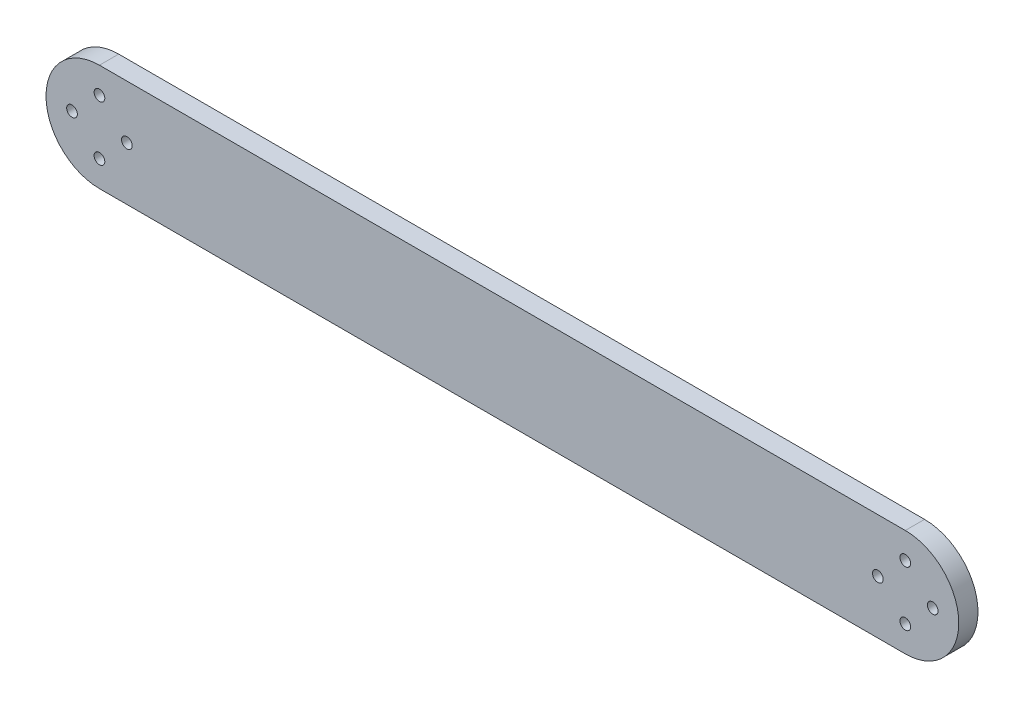
SolidWorks part; units mm, degrees
ref_plane "Front Plane" through (0, 0, 0) normal (0, 0, 1) x (1, 0, 0)
ref_plane "Top Plane" through (0, 0, 0) normal (0, 1, 0) x (1, 0, 0)
ref_plane "Right Plane" through (0, 0, 0) normal (1, 0, 0) x (0, 0, -1)
sketch "Sketch1" plane through (0, 0, 0) normal (0, 0, 1) x (1, 0, 0)
  line L1 (-55.8976, 0) -> (-50.0514, 0) construction
  line L2 (-15, 0.3576) -> (-15, 39.2282) construction
  line L3 (0, -15) -> (226.1538, -15)
  line L4 (0, 15) -> (226.1538, 15)
  line L5 (0, 0) -> (0, 7.7) construction
  line L7 (113.0769, 15) -> (113.0769, 0) construction
  circle A1 centre (0, 0) radius 7.7 construction
  circle A2 centre (0, 7.7) radius 1.5
  circle A3 centre (7.7, 0) radius 1.5
  circle A4 centre (0, -7.7) radius 1.5
  circle A5 centre (-7.7, 0) radius 1.5
  arc A11 (0, 15) -> (0, -15) centre (0, 0) ccw
  circle A12 centre (218.4538, 0) radius 1.5
  circle A13 centre (226.1538, -7.7) radius 1.5
  circle A14 centre (233.8538, 0) radius 1.5
  circle A15 centre (226.1538, 7.7) radius 1.5
  arc A16 (226.1538, 15) -> (226.1538, -15) centre (226.1538, 0) cw
  circle A17 centre (226.1538, 0) radius 13.5 construction
  point P1 (159.5173, 0)
  point P4 (310.2968, 0)
  point P9 (0, 0)
  point P10 (0, 17.5609)
  point P11 (93.2947, 14.7227)
  point P12 (93.5712, 15)
  point P25 (0, 0)
  point P37 (231.4508, 1.1779)
  point P38 (226.1538, 0)
  point P39 (188.5738, 0)
  dimension "D1" = 3
  dimension "D2" = 15.4
  dimension "D4" = 15
  dimension "D3" = 4
extrude "Boss-Extrude1" add sketch "Sketch1" along normal blind 5.4
ref_axis "Axis1" through (0, 0, -0.27) along (0, 0, 1)
